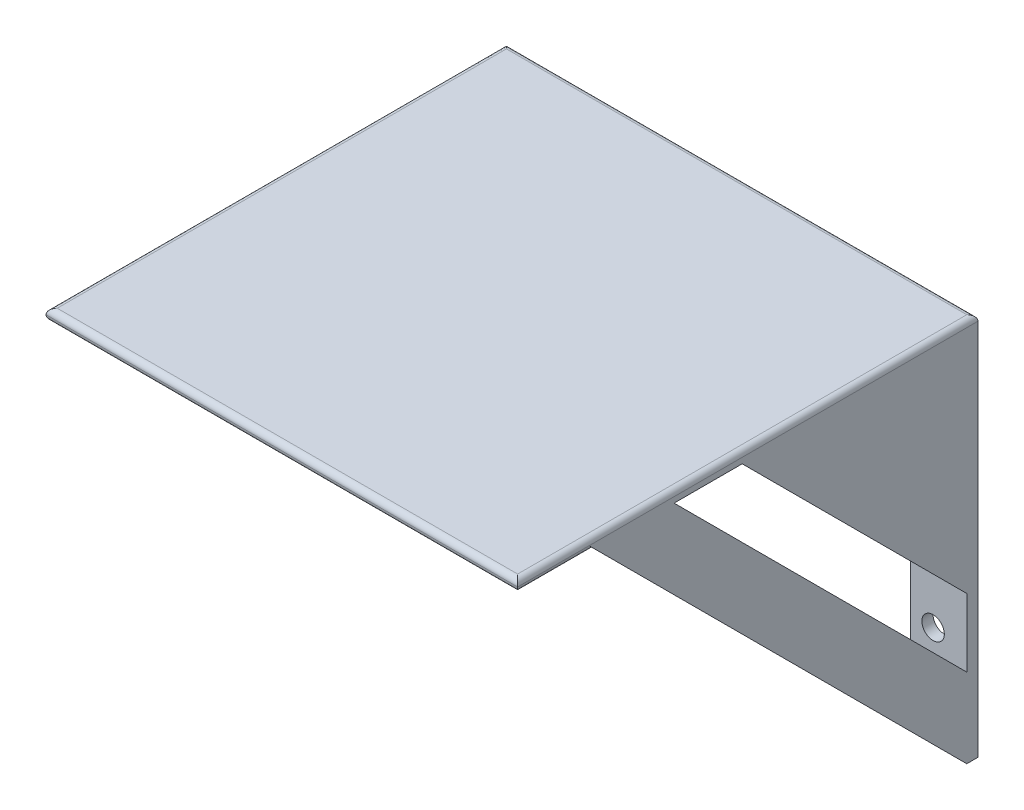
SolidWorks part; units mm, degrees
ref_plane "Front Plane" through (0, 0, 0) normal (0, 0, 1) x (1, 0, 0)
ref_plane "Top Plane" through (0, 0, 0) normal (0, 1, 0) x (1, 0, 0)
ref_plane "Right Plane" through (0, 0, 0) normal (1, 0, 0) x (0, 0, -1)
sketch "Sketch2" plane through (0, 0, 0) normal (0, 0, 1) x (1, 0, 0)
  line L0 (-50.8, -54.1875) -> (-50.8, 12.9125)
  line L1 (-66.675, -54.1875) -> (-50.8, -54.1875)
  line L2 (-66.675, -54.1875) -> (-66.675, 54.1875)
  line L3 (-66.675, 54.1875) -> (66.675, 54.1875)
  line L4 (66.675, -54.1875) -> (66.675, 54.1875)
  line L5 (-66.675, -54.1875) -> (66.675, 54.1875) construction
  line L6 (-66.675, 54.1875) -> (66.675, -54.1875) construction
  line L7 (-25.4, 38.3125) -> (25.4, 38.3125)
  line L8 (50.8, 12.9125) -> (50.8, -54.1875)
  line L9 (50.8, -54.1875) -> (66.675, -54.1875)
  line L10 (-50.8, 12.9125) -> (-25.4, 38.3125)
  line L11 (25.4, 38.3125) -> (50.8, 12.9125)
  point P0 (0, 0)
  point P7 (-50.8, 38.3125)
  point P9 (50.8, 38.3125)
  dimension "D1" = 108.375
  dimension "D2" = 15.875
  dimension "D3" = 15.875
  dimension "D4" = 15.875
  dimension "D5" = 133.35
extrude "Boss-Extrude1" add sketch "Sketch2" along normal blind 3.175
sketch "Sketch3" plane through (0, 0, 3.175) normal (0, 0, 1) x (1, 0, 0)
  line L0 (-66.675, -54.1875) -> (-50.8, -54.1875) construction
  line L2 (-25.4, 38.3125) -> (25.4, 38.3125) construction
  line L3 (-50.8, -54.1875) -> (-50.8, 12.9125) construction
  line L4 (0, 0) -> (0, 69.3516) construction
  circle A0 centre (-57.15, -25.6125) radius 3.175
  circle A1 centre (-57.15, 22.4375) radius 3.175
  circle A2 centre (-34.925, 44.6625) radius 3.175
  circle A3 centre (34.925, 44.6625) radius 3.175
  circle A4 centre (57.15, 22.4375) radius 3.175
  circle A5 centre (57.15, -25.6125) radius 3.175
  dimension "D4" = 6.35
  dimension "D5" = 6.35
  dimension "D7" = 6.35
  dimension "D1" = 28.575
  dimension "D2" = 6.35
  dimension "D3" = 6.35
  dimension "D6" = 15.875
  dimension "D8" = 6.35
  dimension "D9" = 15.875
extrude "Cut-Extrude1" cut sketch "Sketch3" against normal through all
sketch "Sketch4" plane through (0, 0, 3.175) normal (0, 0, 1) x (1, 0, 0)
  line L0 (66.675, -54.1875) -> (66.675, 54.1875) construction
  line L1 (-66.675, 54.1875) -> (66.675, 54.1875)
  line L2 (-66.675, 54.1875) -> (-66.675, 51.0125)
  line L3 (-66.675, 51.0125) -> (66.675, 51.0125)
  line L4 (66.675, 54.1875) -> (66.675, 51.0125)
  dimension "D1" = 3.175
extrude "Boss-Extrude2" add sketch "Sketch4" along normal blind 127
sketch "Sketch5" plane through (-66.675, 0, 0) normal (-1, 0, 0) x (0, 0, 1)
  line L2 (3.175, -12.4875) -> (66.675, 51.0125)
  line L3 (3.175, -12.4875) -> (3.175, 51.0125)
  line L4 (3.175, 51.0125) -> (66.675, 51.0125)
  line L5 (130.175, 51.0125) -> (3.175, 51.0125) construction
  line L6 (108.375, 51.0125) -> (3.175, -54.1875)
  line L7 (3.175, 51.0125) -> (3.175, -54.1875) construction
  line L9 (3.175, -54.1875) -> (0, -54.1875) construction
  line L10 (3.175, -31.7369) -> (85.9244, 51.0125)
  line L11 (3.175, -31.7369) -> (3.175, -54.1875)
  line L12 (85.9244, 51.0125) -> (108.375, 51.0125)
  point P1 (3.175, 51.0125)
  dimension "D1" = 0
  dimension "D2" = 15.875
extrude "Boss-Extrude3" add sketch "Sketch5" against normal blind 3.175
sketch "Sketch6" plane through (66.675, 0, 0) normal (1, 0, 0) x (0, 0, -1)
  line L0 (-108.375, 51.0125) -> (-3.175, -54.1875)
  line L1 (-3.175, -54.1875) -> (-3.175, -31.7369)
  line L2 (-3.175, -12.4875) -> (-66.675, 51.0125)
  line L3 (-66.675, 51.0125) -> (-3.175, 51.0125)
  line L4 (-3.175, 51.0125) -> (-3.175, -12.4875)
  line L5 (-3.175, -31.7369) -> (-85.9244, 51.0125)
  line L6 (-85.9244, 51.0125) -> (-108.375, 51.0125)
  point P1 (-3.175, 51.0125)
extrude "Boss-Extrude4" add sketch "Sketch6" against normal blind 3.175
fillet "Fillet2" radius 1.5875 7 edges at (66.675, 54.1875, 65.0875) (0, 54.1875, 130.175) (-66.675, 54.1875, 65.0875) (0, 54.1875, 0) (66.675, 51.0125, 119.275) (0, 51.0125, 130.175) (-66.675, 51.0125, 119.275)
